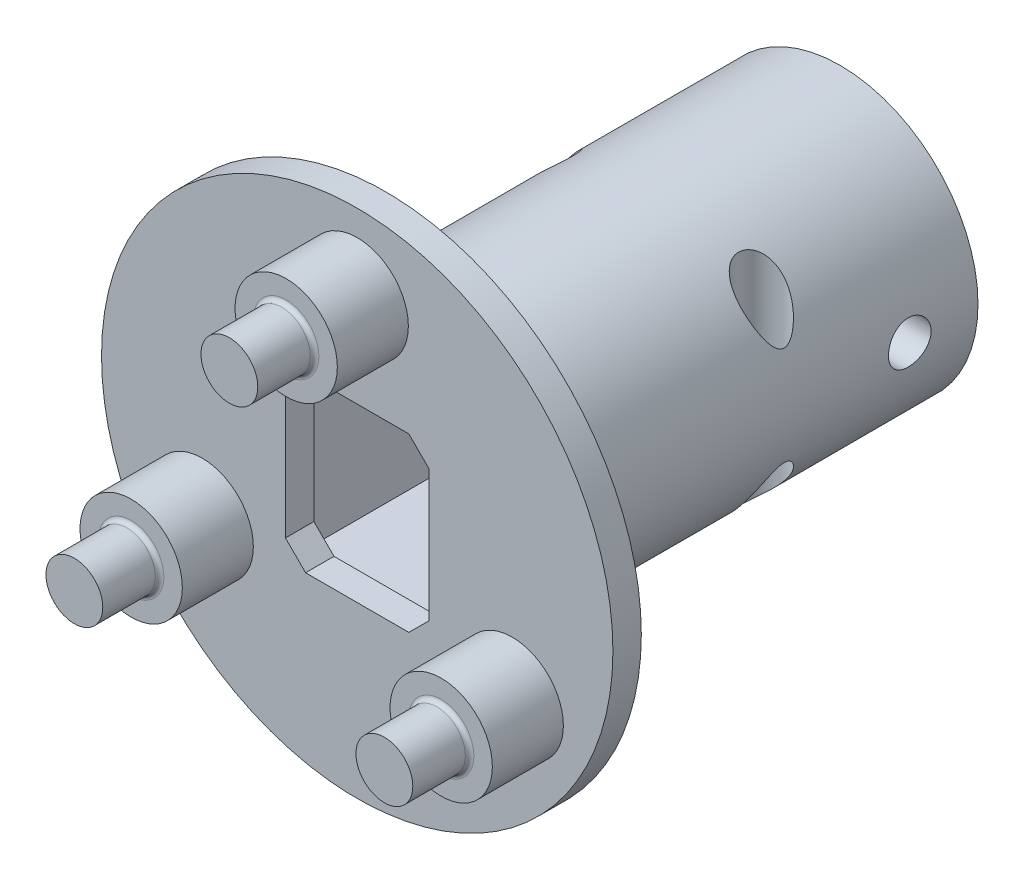
SolidWorks part; units mm, degrees
ref_plane "Front" through (0, 0, 0) normal (0, 0, 1) x (1, 0, 0)
ref_plane "Top" through (0, 0, 0) normal (0, 1, 0) x (1, 0, 0)
ref_plane "Right" through (0, 0, 0) normal (1, 0, 0) x (0, 0, -1)
sketch "Sketch1" plane through (0, 0, 0) normal (0, 0, 1) x (1, 0, 0)
  line L0 (-2.3795, 0) -> (0, 0) construction
  line L1 (-5.05, 6.05) -> (5.05, 6.05)
  line L2 (-5.05, 6.05) -> (-5.05, -6.05)
  line L3 (-5.05, -6.05) -> (5.05, -6.05)
  line L4 (5.05, 6.05) -> (5.05, -6.05)
  line L5 (0, 0) -> (0, 2.6131) construction
  circle A0 centre (0, 0) radius 9.7
  dimension "D3" = 19.4
  dimension "D1" = 12.1
  dimension "D2" = 10.1
extrude "Boss-Extrude1" add sketch "Sketch1" along normal blind 34
sketch "Sketch5" plane through (0, 0, 34) normal (0, 0, 1) x (1, 0, 0)
  arc A144 (-3.9021, 8.8658) -> (-5.9774, 10.9782) centre (-7.9711, 6.944) ccw
  arc A145 (-5.9774, 10.9782) -> (-6.5187, 10.6657) centre (0, 0) ccw
  arc A146 (-6.5187, 10.6657) -> (-5.7269, 7.8122) centre (-2.0281, 10.3752) ccw
  arc A147 (-5.7269, 7.8122) -> (-6.6991, 6.9965) centre (0, 0) ccw
  arc A148 (-6.6991, 6.9965) -> (-9.3717, 8.2717) centre (-9.8654, 3.7989) ccw
  arc A149 (-9.3717, 8.2717) -> (-9.7734, 7.7929) centre (0, 0) ccw
  arc A150 (-9.7734, 7.7929) -> (-8.0535, 5.3824) centre (-5.4543, 9.0558) ccw
  arc A151 (-8.0535, 5.3824) -> (-8.688, 4.2833) centre (0, 0) ccw
  arc A152 (-8.688, 4.2833) -> (-11.6356, 4.5676) centre (-10.5697, 0.1956) ccw
  arc A153 (-11.6356, 4.5676) -> (-11.8494, 3.9803) centre (0, 0) ccw
  arc A154 (-11.8494, 3.9803) -> (-9.4087, 2.3033) centre (-8.2226, 6.6442) ccw
  arc A155 (-9.4087, 2.3033) -> (-9.629, 1.0535) centre (0, 0) ccw
  arc A156 (-9.629, 1.0535) -> (-12.4961, 0.3125) centre (-9.9992, -3.4312) ccw
  arc A157 (-12.4961, 0.3125) -> (-12.4961, -0.3125) centre (0, 0) ccw
  arc A158 (-12.4961, -0.3125) -> (-9.629, -1.0535) centre (-9.9992, 3.4312) ccw
  arc A159 (-9.629, -1.0535) -> (-9.4087, -2.3033) centre (0, 0) ccw
  arc A160 (-9.4087, -2.3033) -> (-11.8494, -3.9803) centre (-8.2226, -6.6442) ccw
  arc A161 (-11.8494, -3.9803) -> (-11.6356, -4.5676) centre (0, 0) ccw
  arc A162 (-11.6356, -4.5676) -> (-8.688, -4.2833) centre (-10.5697, -0.1956) ccw
  arc A163 (-8.688, -4.2833) -> (-8.0535, -5.3824) centre (0, 0) ccw
  arc A164 (-8.0535, -5.3824) -> (-9.7734, -7.7929) centre (-5.4543, -9.0558) ccw
  arc A165 (-9.7734, -7.7929) -> (-9.3717, -8.2717) centre (0, 0) ccw
  arc A166 (-9.3717, -8.2717) -> (-6.6991, -6.9965) centre (-9.8654, -3.7989) ccw
  arc A167 (-6.6991, -6.9965) -> (-5.7269, -7.8122) centre (0, 0) ccw
  arc A168 (-5.7269, -7.8122) -> (-6.5187, -10.6657) centre (-2.0281, -10.3752) ccw
  arc A169 (-6.5187, -10.6657) -> (-5.9774, -10.9782) centre (0, 0) ccw
  arc A170 (-5.9774, -10.9782) -> (-3.9021, -8.8658) centre (-7.9711, -6.944) ccw
  arc A171 (-3.9021, -8.8658) -> (-2.7096, -9.2998) centre (0, 0) ccw
  arc A172 (-2.7096, -9.2998) -> (-2.4777, -12.252) centre (1.6428, -10.4431) ccw
  arc A173 (-2.4777, -12.252) -> (-1.8622, -12.3605) centre (0, 0) ccw
  arc A174 (-1.8622, -12.3605) -> (-0.6346, -9.6657) centre (-5.1154, -9.2515) ccw
  arc A175 (-0.6346, -9.6657) -> (0.6346, -9.6657) centre (0, 0) ccw
  arc A176 (0.6346, -9.6657) -> (1.8622, -12.3605) centre (5.1154, -9.2515) ccw
  arc A177 (1.8622, -12.3605) -> (2.4777, -12.252) centre (0, 0) ccw
  arc A178 (2.4777, -12.252) -> (2.7096, -9.2998) centre (-1.6428, -10.4431) ccw
  arc A179 (2.7096, -9.2998) -> (3.9021, -8.8658) centre (0, 0) ccw
  arc A180 (3.9021, -8.8658) -> (5.9774, -10.9782) centre (7.9711, -6.944) ccw
  arc A181 (5.9774, -10.9782) -> (6.5187, -10.6657) centre (0, 0) ccw
  arc A182 (6.5187, -10.6657) -> (5.7269, -7.8122) centre (2.0281, -10.3752) ccw
  arc A183 (5.7269, -7.8122) -> (6.6991, -6.9965) centre (0, 0) ccw
  arc A184 (6.6991, -6.9965) -> (9.3717, -8.2717) centre (9.8654, -3.7989) ccw
  arc A185 (9.3717, -8.2717) -> (9.7734, -7.7929) centre (0, 0) ccw
  arc A186 (9.7734, -7.7929) -> (8.0535, -5.3824) centre (5.4543, -9.0558) ccw
  arc A187 (8.0535, -5.3824) -> (8.688, -4.2833) centre (0, 0) ccw
  arc A188 (8.688, -4.2833) -> (11.6356, -4.5676) centre (10.5697, -0.1956) ccw
  arc A189 (11.6356, -4.5676) -> (11.8494, -3.9803) centre (0, 0) ccw
  arc A190 (11.8494, -3.9803) -> (9.4087, -2.3033) centre (8.2226, -6.6442) ccw
  arc A191 (9.4087, -2.3033) -> (9.629, -1.0535) centre (0, 0) ccw
  arc A192 (9.629, -1.0535) -> (12.4961, -0.3125) centre (9.9992, 3.4312) ccw
  arc A193 (12.4961, -0.3125) -> (12.4961, 0.3125) centre (0, 0) ccw
  arc A194 (12.4961, 0.3125) -> (9.629, 1.0535) centre (9.9992, -3.4312) ccw
  arc A195 (9.629, 1.0535) -> (9.4087, 2.3033) centre (0, 0) ccw
  arc A196 (9.4087, 2.3033) -> (11.8494, 3.9803) centre (8.2226, 6.6442) ccw
  arc A197 (11.8494, 3.9803) -> (11.6356, 4.5676) centre (0, 0) ccw
  arc A198 (11.6356, 4.5676) -> (8.688, 4.2833) centre (10.5697, 0.1956) ccw
  arc A199 (8.688, 4.2833) -> (8.0535, 5.3824) centre (0, 0) ccw
  arc A200 (8.0535, 5.3824) -> (9.7734, 7.7929) centre (5.4543, 9.0558) ccw
  arc A201 (9.7734, 7.7929) -> (9.3717, 8.2717) centre (0, 0) ccw
  arc A202 (9.3717, 8.2717) -> (6.6991, 6.9965) centre (9.8654, 3.7989) ccw
  arc A203 (6.6991, 6.9965) -> (5.7269, 7.8122) centre (0, 0) ccw
  arc A204 (5.7269, 7.8122) -> (6.5187, 10.6657) centre (2.0281, 10.3752) ccw
  arc A205 (6.5187, 10.6657) -> (5.9774, 10.9782) centre (0, 0) ccw
  arc A206 (5.9774, 10.9782) -> (3.9021, 8.8658) centre (7.9711, 6.944) ccw
  arc A207 (3.9021, 8.8658) -> (2.7096, 9.2998) centre (0, 0) ccw
  arc A208 (2.7096, 9.2998) -> (2.4777, 12.252) centre (-1.6428, 10.4431) ccw
  arc A209 (2.4777, 12.252) -> (1.8622, 12.3605) centre (0, 0) ccw
  arc A210 (1.8622, 12.3605) -> (0.6346, 9.6657) centre (5.1154, 9.2515) ccw
  arc A211 (0.6346, 9.6657) -> (-0.6346, 9.6657) centre (0, 0) ccw
  arc A212 (-0.6346, 9.6657) -> (-1.8622, 12.3605) centre (-5.1154, 9.2515) ccw
  arc A213 (-1.8622, 12.3605) -> (-2.4777, 12.252) centre (0, 0) ccw
  arc A214 (-2.4777, 12.252) -> (-2.7096, 9.2998) centre (1.6428, 10.4431) ccw
  arc A215 (-2.7096, 9.2998) -> (-3.9021, 8.8658) centre (0, 0) ccw
extrude "Boss-Extrude2" add sketch "Sketch5" against normal blind 4
sketch "Sketch7" plane through (0, 0, 30) normal (0, 0, -1) x (-1, 0, 0)
  line L4 (5.05, -6.05) -> (5.05, 6.05)
  line L5 (5.05, 6.05) -> (-5.05, 6.05)
  line L6 (-5.05, 6.05) -> (-5.05, -6.05)
  line L7 (-5.05, -6.05) -> (5.05, -6.05)
  line L8 (5.05, -6.05) -> (5.05, 6.05)
  line L9 (5.05, 6.05) -> (-5.05, 6.05)
  line L10 (-5.05, 6.05) -> (-5.05, -6.05)
  line L11 (-5.05, -6.05) -> (5.05, -6.05)
  dimension "D1" = 0
extrude "Cut-Extrude3" cut sketch "Sketch7" against normal offset from surface (2 mm away) 2 up to face at (0, 0, 34)
sketch "Sketch8" plane through (0, 0, 32) normal (0, 0, -1) x (-1, 0, 0)
  line L0 (-5.05, 6.05) -> (-5.05, -6.05) construction
  line L1 (-5.05, -6.05) -> (5.05, -6.05) construction
  line L4 (-5.05, -4.6358) -> (-3.6358, -6.05)
  line L5 (-5.05, 0) -> (-3.2683, 0) construction
  line L6 (0, -6.05) -> (0, -3.3776) construction
  line L7 (-5.05, 4.6358) -> (-3.6358, 6.05)
  line L11 (5.05, -4.6358) -> (3.6358, -6.05)
  line L15 (5.05, 4.6358) -> (3.6358, 6.05)
  line L20 (-5.05, -6.05) -> (5.05, -6.05)
  line L21 (5.05, -6.05) -> (5.05, 6.05)
  line L22 (5.05, 6.05) -> (-5.05, 6.05)
  line L23 (-5.05, 6.05) -> (-5.05, -6.05)
  line L24 (-3.6358, -6.05) -> (3.6358, -6.05)
  line L25 (5.05, -4.6358) -> (5.05, 4.6358)
  line L26 (3.6358, 6.05) -> (-3.6358, 6.05)
  line L27 (-5.05, 4.6358) -> (-5.05, -4.6358)
  dimension "D2" = 2
  dimension "D3" = 0
extrude "Cut-Extrude4" cut sketch "Sketch8" against normal up to next
sketch "Sketch10" plane through (0, 0, 0) normal (0, 1, 0) x (1, 0, 0)
  line L0 (0, 0) -> (0, -21.7379) construction
  line L1 (5.05, 0) -> (-5.05, 0) construction
  circle A0 centre (7.45, -13) radius 1.6
  circle A1 centre (-7.45, -13) radius 1.6
  dimension "D1" = 3.2
  dimension "D2" = 14.9
  dimension "D3" = 13
  dimension "D4" = 21.7379
extrude "Cut-Extrude5" cut sketch "Sketch10" against normal through all both and the other way through all
sketch "Sketch12" plane through (5.05, 0, 0) normal (-1, 0, 0) x (0, 0, 1)
  circle A0 centre (4.8, 0) radius 1.5
  dimension "D1" = 3
  dimension "D2" = 4.8
extrude "Cut-Extrude6" cut sketch "Sketch12" against normal through all both and the other way through all
sketch "Sketch13" plane through (0, 0, 0) normal (0, 0, -1) x (-1, 0, 0)
  circle A0 centre (0, 0) radius 9.7 construction
  circle A1 centre (0, 0) radius 9.7
extrude "Cut-Extrude-Thin1" cut sketch "Sketch13" against normal through all thin thin type one direction wall 5
sketch "Sketch15" plane through (0, 0, 34) normal (0, 0, 1) x (1, 0, 0)
  circle A0 centre (0, 0) radius 18
  circle A1 centre (0, 0) radius 9.7
  circle A2 centre (0, 0) radius 9.7
  dimension "D2" = 36
  dimension "D1" = 0
extrude "Boss-Extrude3" add sketch "Sketch15" against normal blind 2
sketch "Sketch26" plane through (0, 0, 34) normal (0, 0, 1) x (1, 0, 0)
  circle A0 centre (0, 12.6) radius 3.6
  dimension "D1" = 7.2
  dimension "D2" = 12.6
extrude "Boss-Extrude9" add sketch "Sketch26" along normal blind 12.5
sketch "Sketch27" plane through (0, 0, 46.5) normal (0, 0, 1) x (1, 0, 0)
  circle A0 centre (0, 12.6) radius 2
  circle A1 centre (0, 12.6) radius 3.6 construction
  dimension "D1" = 4
extrude "Boss-Extrude10" add sketch "Sketch27" along normal blind 5.5
pattern_circular "CirPattern1" count 3 over 360 about axis through (0, 0, 34) along (0, 0, -1) of "Boss-Extrude9", "Boss-Extrude10"
sketch "Sketch19" plane through (0, 0, 32) normal (0, 0, -1) x (-1, 0, 0)
  line L0 (0, 0) -> (0, 70) construction
  line L1 (0, 0) -> (0.8188, 0.298) construction
  line L2 (0, 0) -> (15.317, 5.5749) construction
  circle A0 centre (15.317, 5.5749) radius 2.5
  circle A1 centre (0, 0) radius 18 construction
  dimension "D1" = 18.8
  dimension "D2" = 5
  dimension "D3" = 70
extrude "Boss-Extrude6" add sketch "Sketch19" along normal blind 4
sketch "Sketch20" plane through (0, 0, 0) normal (0, 0, -1) x (-1, 0, 0)
  line L0 (-5.05, -6.05) -> (-5.05, 6.05) construction
  line L1 (-5.05, 6.05) -> (5.05, 6.05) construction
  line L2 (5.05, 6.05) -> (5.05, -6.05) construction
  line L3 (5.05, -6.05) -> (-5.05, -6.05) construction
  line L4 (-5.05, -6.05) -> (-5.05, 6.05)
  line L5 (-5.05, 6.05) -> (5.05, 6.05)
  line L6 (5.05, 6.05) -> (5.05, -6.05)
  line L7 (5.05, -6.05) -> (-5.05, -6.05)
extrude "Cut-Extrude-Thin2" cut sketch "Sketch20" against normal offset from surface (21.5 mm away) 10.5 thin up to face at (-5.05, 5.1072, 32) thin type one direction wall 0.1
chamfer "Chamfer1" distance 0.1 angle 45 4 edges at (5.05, 0, 21.5) (0, 6.05, 21.5) (0, -6.05, 21.5) (-5.05, 0, 21.5)
sketch "Sketch23" plane through (0, 0, 0) normal (0, 0, -1) x (-1, 0, 0)
  line L5 (5.15, -6.15) -> (5.15, 6.15)
  line L6 (-5.15, -6.15) -> (5.15, -6.15)
  line L7 (-5.15, 6.15) -> (-5.15, -6.15)
  line L8 (5.15, 6.15) -> (-5.15, 6.15)
  line L9 (5.15, -6.15) -> (5.15, 6.15)
  line L10 (-5.15, -6.15) -> (5.15, -6.15)
  line L11 (-5.15, 6.15) -> (-5.15, -6.15)
  line L12 (5.15, 6.15) -> (-5.15, 6.15)
  dimension "D1" = 0
extrude "Cut-Extrude7" cut sketch "Sketch23" against normal up to surface (32 mm away) up to face at (5.05, -5.1072, 32)
sketch "Sketch28" plane through (0, 0, 28) normal (0, 0, -1) x (-1, 0, 0)
  arc A0 (14.7709, 3.1353) -> (13.3305, 7.0928) centre (0, 0) ccw
  arc A1 (17.0816, 3.804) -> (15.5304, 8.0658) centre (0, 0) ccw
  circle A2 centre (15.317, 5.5749) radius 2.5 construction
  arc A3 (13.3305, 7.0928) -> (14.7709, 3.1353) centre (15.317, 5.5749) ccw
  arc A4 (17.0816, 3.804) -> (15.5304, 8.0658) centre (15.317, 5.5749) ccw
  dimension "D1" = 30.2
  dimension "D2" = 35
extrude "Cut-Extrude8" cut sketch "Sketch28" against normal up to surface (4 mm away) up to face at (9.7, 0, 32)
fillet "Fillet1" radius 0.3 2 edges at (-14.3057, 7.8613, 32) (-16.0119, 3.1735, 32)
sketch "Sketch29" plane through (0, 0, 46.5) normal (0, 0, 1) x (1, 0, 0)
  circle A0 centre (-10.9119, -6.3) radius 2 construction
  circle A1 centre (-10.9119, -6.3) radius 3.6 construction
  circle A2 centre (-10.9119, -6.3) radius 2
  circle A3 centre (-10.9119, -6.3) radius 3.6
  circle A4 centre (10.9119, -6.3) radius 3.6 construction
  circle A5 centre (10.9119, -6.3) radius 2 construction
  circle A6 centre (10.9119, -6.3) radius 3.6
  circle A7 centre (10.9119, -6.3) radius 2
  circle A8 centre (0, 12.6) radius 2 construction
  circle A9 centre (0, 12.6) radius 3.6 construction
  circle A10 centre (0, 12.6) radius 2
  circle A11 centre (0, 12.6) radius 3.6
extrude "Cut-Extrude9" cut sketch "Sketch29" against normal blind 0.5
sketch "Sketch30" plane through (0, 0, 52) normal (0, 0, 1) x (1, 0, 0)
  circle A0 centre (0, 12.6) radius 2 construction
  circle A1 centre (-10.9119, -6.3) radius 2
  circle A2 centre (-10.9119, -6.3) radius 2
  circle A3 centre (10.9119, -6.3) radius 2 construction
  circle A4 centre (0, 12.6) radius 2
  circle A5 centre (10.9119, -6.3) radius 2
  dimension "D1" = 0
extrude "Cut-Extrude10" cut sketch "Sketch30" against normal blind 0.5
sketch "Sketch31" plane through (0, 0, 46) normal (0, 0, 1) x (1, 0, 0)
  circle A0 centre (10.9119, -6.3) radius 2 construction
  circle A1 centre (0, 12.6) radius 3.6
  circle A2 centre (0, 12.6) radius 3.6
  circle A3 centre (-10.9119, -6.3) radius 3.6
  circle A4 centre (-10.9119, -6.3) radius 3.6
  circle A5 centre (10.9119, -6.3) radius 3.6
  circle A6 centre (10.9119, -6.3) radius 3.6
  circle A7 centre (-10.9119, -6.3) radius 2 construction
  circle A8 centre (0, 12.6) radius 2 construction
  circle A9 centre (10.9119, -6.3) radius 2
  circle A10 centre (-10.9119, -6.3) radius 2
  circle A11 centre (0, 12.6) radius 2
  dimension "D1" = 0
  dimension "D2" = 0
  dimension "D3" = 0
extrude "Cut-Extrude11" cut sketch "Sketch31" against normal blind 7
sketch "Sketch32" plane through (0, 0, 51.5) normal (0, 0, 1) x (1, 0, 0)
  circle A1 centre (-10.9119, -6.3) radius 2
  circle A2 centre (-10.9119, -6.3) radius 2
  circle A3 centre (0, 12.6) radius 2
  circle A4 centre (0, 12.6) radius 2
  circle A5 centre (10.9119, -6.3) radius 2
  circle A6 centre (10.9119, -6.3) radius 2
  dimension "D1" = 0
  dimension "D2" = 0
  dimension "D3" = 0
extrude "Cut-Extrude12" cut sketch "Sketch32" against normal blind 8.5
fillet "Fillet2" radius 0.3 3 edges at (12.9119, -6.3, 39) (-8.9119, -6.3, 39) (2, 12.6, 39)
